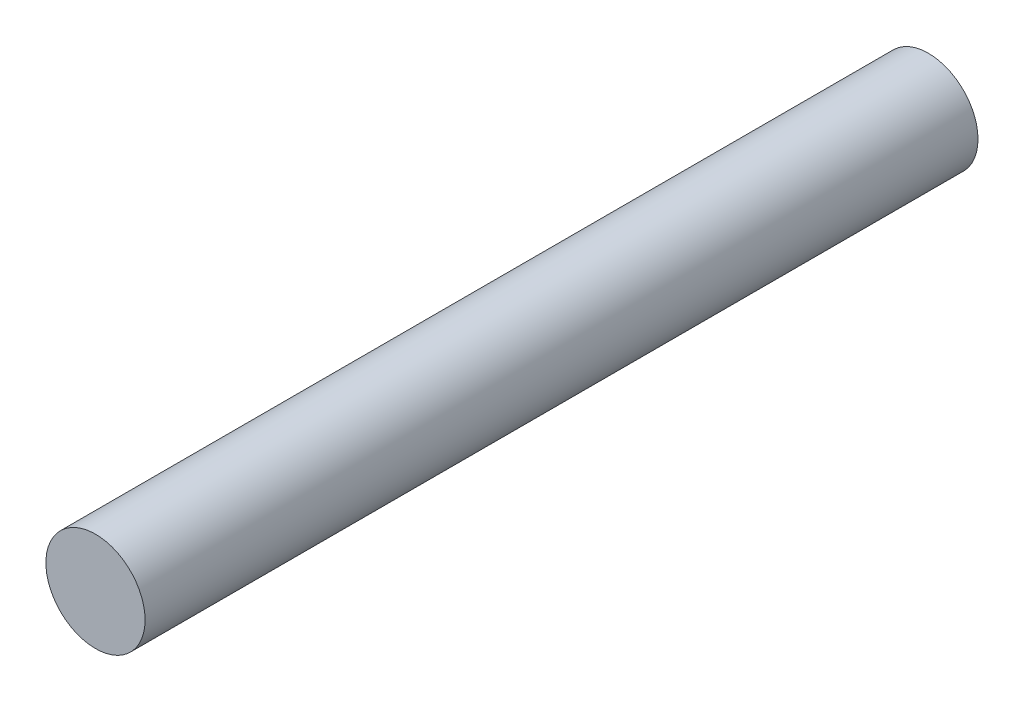
SolidWorks part; units mm, degrees
ref_plane "Front Plane" through (0, 0, 0) normal (0, 0, 1) x (1, 0, 0)
ref_plane "Top Plane" through (0, 0, 0) normal (0, 1, 0) x (1, 0, 0)
ref_plane "Right Plane" through (0, 0, 0) normal (1, 0, 0) x (0, 0, -1)
sketch "Sketch1" plane through (0, 0, 0) normal (0, 0, 1) x (1, 0, 0)
  circle A0 centre (0, 0) radius 4.7625
  point P2 (0, 0)
  dimension "D1" = 9.525
extrude "Boss-Extrude1" add sketch "Sketch1" along normal blind 80
ref_axis "Axis1" through (0, 0, 80) along (0, 0, -1)
